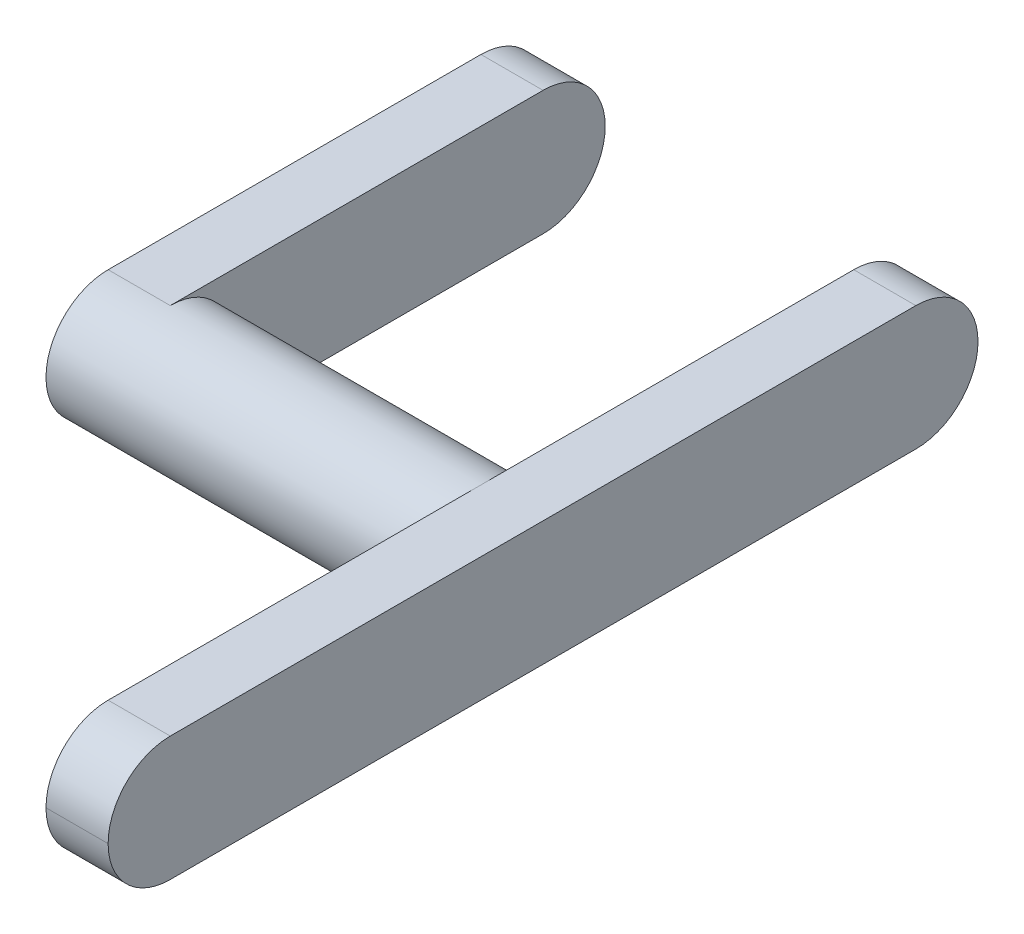
SolidWorks part; units mm, degrees
ref_plane "Ön Düzlem" through (0, 0, 0) normal (0, 0, 1) x (1, 0, 0)
ref_plane "Üst Düzlem" through (0, 0, 0) normal (0, 1, 0) x (1, 0, 0)
ref_plane "Sağ Düzlem" through (0, 0, 0) normal (1, 0, 0) x (0, 0, -1)
sketch "Çizim1" plane through (0, 0, 0) normal (0, 1, 0) x (1, 0, 0)
  line L1 (0, 0) -> (5, 0)
  line L2 (0, 0) -> (0, 70)
  line L3 (0, 70) -> (5, 70)
  line L4 (5, 0) -> (5, 70)
  dimension "D1" = 70
  dimension "D2" = 5
extrude "Yükseklik-Ekstrüzyon1" add sketch "Çizim1" along normal blind 10
sketch "Çizim2" plane through (0, 0, 0) normal (-1, 0, 0) x (0, 0, 1)
  line L0 (-70, 10) -> (0, 10) construction
  line L1 (-70, 0) -> (-15, 0)
  line L2 (-70, 0) -> (-70, 10)
  line L3 (-70, 10) -> (-15, 10)
  line L4 (0, 10) -> (0, 0) construction
  circle A0 centre (-35, 5) radius 5
  dimension "D2" = 10
  dimension "D1" = 35
sketch "Çizim3" plane through (0, 0, 0) normal (-1, 0, 0) x (0, 0, 1)
  line L0 (0, 10) -> (0, 0) construction
  line L1 (-70, 0) -> (0, 0) construction
  line L2 (-5.3055, 8.4866) -> (-12, 7.9)
  line L3 (-12, 7.9) -> (-12, 2.1)
  line L4 (-12, 2.1) -> (-5.3055, 1.5134)
  circle A0 centre (-5, 5) radius 3.5
  point P8 (-12, 8.0002)
  point P11 (0, 0)
  dimension "D1" = 7
  dimension "D2" = 5
  dimension "D3" = 5
  dimension "D4" = 12
  dimension "D5" = 5.8
extrude "Kes-Ekstrüzyon2" cut sketch "Çizim3" against normal blind 3.5 contours A0 | A0 L2 L3 L4 region at (0, 5, -9.8164) region at (0, 5, -5)
extrude "Yükseklik-Ekstrüzyon4" add sketch "Çizim2" along normal blind 25 contours A0 region at (0, 5, -35)
fillet "Radyus1" radius 5 4 edges at (2.5, 0, -70) (2.5, 0, 0) (2.5, 10, 0) (2.5, 10, -70)
sketch "Çizim4" plane through (-25, 0, 0) normal (-1, 0, 0) x (0, 0, 1)
  line L0 (-35, 5) -> (-65, 5) construction
  line L1 (-35, 0) -> (-65, 0)
  line L2 (-35, 10) -> (-65, 10)
  line L3 (-65, 10) -> (-35, 10) construction
  arc A0 (-35, 0) -> (-35, 10) centre (-35, 5) ccw
  arc A1 (-65, 10) -> (-65, 0) centre (-65, 5) ccw
  arc A2 (-65, 10) -> (-70, 5) centre (-65, 5) ccw construction
  point P2 (-50, 5)
extrude "Yükseklik-Ekstrüzyon5" add sketch "Çizim4" along normal blind 5
